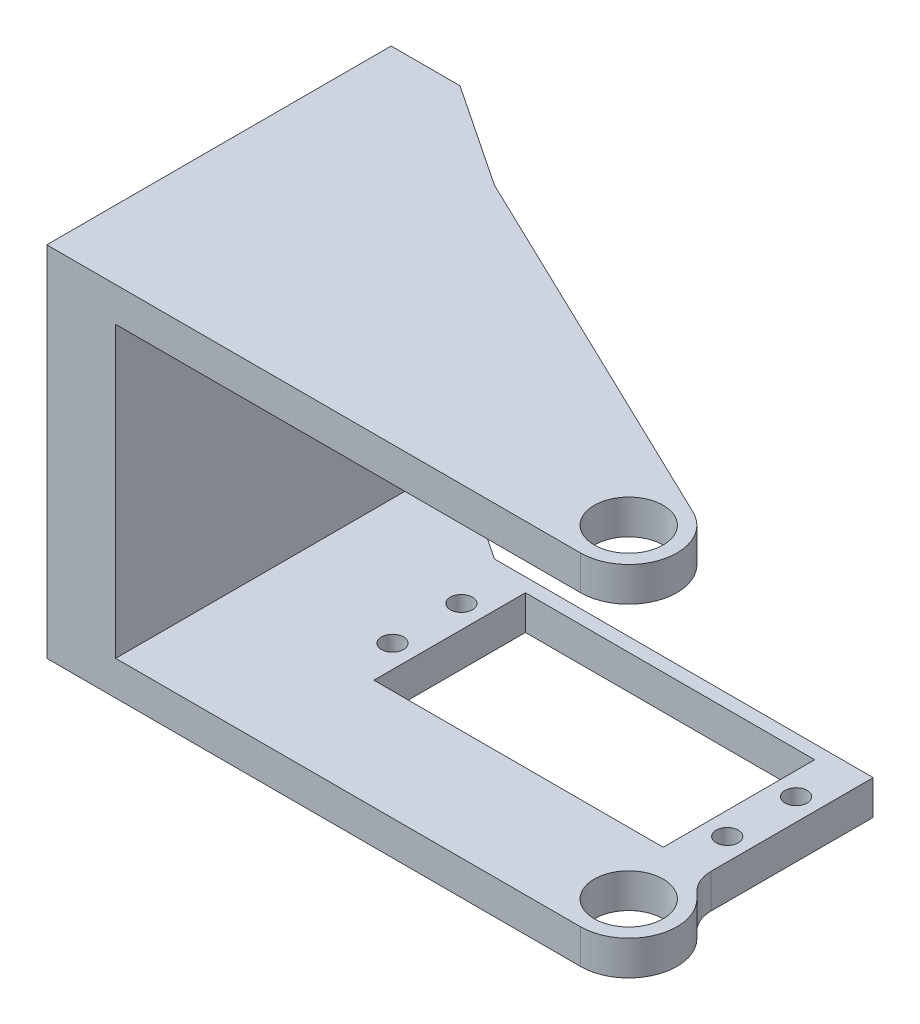
SolidWorks part; units mm, degrees
ref_plane "Front Plane" through (0, 0, 0) normal (0, 0, 1) x (1, 0, 0)
ref_plane "Top Plane" through (0, 0, 0) normal (0, 1, 0) x (1, 0, 0)
ref_plane "Right Plane" through (0, 0, 0) normal (1, 0, 0) x (0, 0, -1)
ref_axis "X" through (-88.99, 0, 0) along (1, 0, 0)
ref_axis "Y" through (0, 55, 0) along (0, -1, 0)
ref_axis "Z" through (0, 0, -88.99) along (0, 0, 1)
sketch "Sketch1" plane through (0, 0, 0) normal (0, 1, 0) x (1, 0, 0)
  line L0 (4.9497, 4.9497) -> (3.9645, 5.935)
  line L1 (2.5, 9.4706) -> (2.5, 33)
  line L2 (2.5, 33) -> (-52.5, 33)
  line L3 (-52.5, 33) -> (-52.5, -7)
  line L4 (0, -7) -> (-52.5, -7)
  line L5 (-25, 20) -> (-25, 33) construction
  line L6 (-49.3, 25) -> (-0.7, 25) construction
  line L7 (-49.3, 25) -> (-49.3, 15) construction
  line L8 (-49.3, 15) -> (-0.7, 15) construction
  line L9 (-0.7, 25) -> (-0.7, 15) construction
  line L10 (-49.3, 25) -> (-0.7, 15) construction
  line L11 (-49.3, 15) -> (-0.7, 25) construction
  line L12 (-52.5, -7) -> (-77.5, -7)
  line L13 (-46, 31) -> (-4, 31)
  line L14 (-46, 31) -> (-46, 9)
  line L15 (-46, 9) -> (-4, 9)
  line L16 (-4, 31) -> (-4, 9)
  line L17 (-46, 31) -> (-4, 9) construction
  line L18 (-46, 9) -> (-4, 31) construction
  line L19 (-67.5, 43) -> (-77.5, 43)
  line L20 (-67.5, 43) -> (-52.5, 33)
  line L21 (-77.5, 43) -> (-77.5, -7)
  line L22 (-67.5, 43) -> (-67.5, -7)
  circle A0 centre (0, 0) radius 5
  arc A1 (0, -7) -> (4.9497, 4.9497) centre (0, 0) ccw
  arc A2 (3.9645, 5.935) -> (2.5, 9.4706) centre (7.5, 9.4706) cw
  circle A3 centre (-0.7, 25) radius 1.6
  circle A4 centre (-0.7, 15) radius 1.6
  circle A5 centre (-49.3, 15) radius 1.6
  circle A6 centre (-49.3, 25) radius 1.6
  point P18 (-25, 20)
  point P30 (-58.8326, -7)
  dimension "D1" = 10
  dimension "D2" = 45
  dimension "D3" = 2
  dimension "D4" = 5
  dimension "D5" = 3.2
  dimension "D6" = 42
  dimension "D7" = 22
  dimension "D8" = 48.6
  dimension "D9" = 10
  dimension "D10" = 25
  dimension "D11" = 20
  dimension "D12" = 55
  dimension "D13" = 2
  dimension "D14" = 50
  dimension "D15" = 10
  dimension "D16" = 15
extrude "Boss-Extrude1" add sketch "Sketch1" against normal blind 5 contours L0 A2 L1 L2 L3 L4 A1 A6 A5 A4 A3 L13 L16 L15 L14 A0 region at (-25.5649, 0, -7.8484)
extrude "Boss-Extrude2" add sketch "Sketch1<4>" against normal up to surface (5 mm away) contours L20 L22 L12 L3 region at (-60.2778, 0, -15.5926) up to face at (-49.3, -5, -23.4)
sketch "Sketch1<4>" plane through (0, 0, 0) normal (0, 1, 0) x (1, 0, 0) same geometry as "Sketch1"
sketch "Sketch2" plane through (0, 0, 0) normal (0, 1, 0) x (1, 0, 0)
  line L0 (-67.5, 43) -> (-52.5, 33) construction
  line L4 (0, -7) -> (-52.5, -7) construction
  line L5 (-52.5, -7) -> (-77.5, -7) construction
  line L6 (-77.5, 43) -> (-77.5, -7) construction
  line L7 (-67.5, 43) -> (-77.5, 43) construction
  line L8 (-67.5, 43) -> (-52.5, 33)
  line L12 (0, -7) -> (-52.5, -7)
  line L13 (-52.5, -7) -> (-77.5, -7)
  line L14 (-77.5, 43) -> (-77.5, -7)
  line L15 (-67.5, 43) -> (-77.5, 43)
  line L16 (-52.5, 33) -> (3.0324, 6.3091)
  circle A1 centre (0, 0) radius 5 construction
  arc A2 (0, -7) -> (4.9497, 4.9497) centre (0, 0) ccw construction
  circle A4 centre (0, 0) radius 5
  arc A5 (0, -7) -> (3.0324, 6.3091) centre (0, 0) ccw
  point P2 (3.9645, 5.7654)
  point P6 (3.9699, 5.6731)
ref_plane "Plane1" through (0, 42, 0) normal (0, 1, 0) x (1, 0, 0)
extrude "Boss-Extrude4" add sketch "Sketch2" along normal blind 5 from surface separate body starting at plane "Plane1"
extrude "Boss-Extrude3" add sketch "Sketch1<5>" against normal up to surface (5 mm away) and the other way up to surface (42 mm away) contours L22 L19 L21 L12 region at (-72.5, 0, -18) up to face at (-49.3, -5, -23.4) other way up to plane "Plane1"
sketch "Sketch1<5>" plane through (0, 0, 0) normal (0, 1, 0) x (1, 0, 0) same geometry as "Sketch1"
